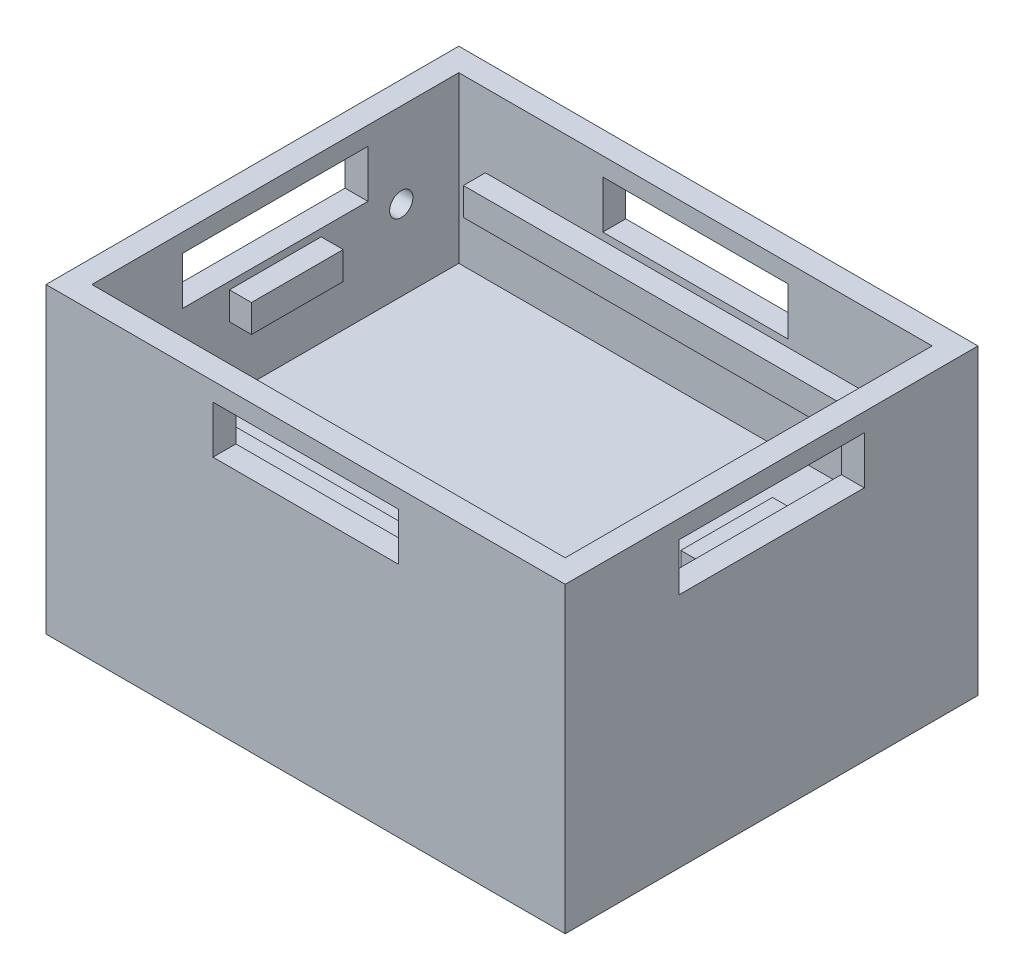
SolidWorks part; units mm, degrees
ref_plane "Front Plane" through (0, 0, 0) normal (0, 0, 1) x (1, 0, 0)
ref_plane "Top Plane" through (0, 0, 0) normal (0, 1, 0) x (1, 0, 0)
ref_plane "Right Plane" through (0, 0, 0) normal (1, 0, 0) x (0, 0, -1)
sketch "Sketch1" plane through (0, 0, 0) normal (0, 1, 0) x (1, 0, 0)
  line L0 (-2.5, 2.5) -> (-2.5, 202.5)
  line L5 (-15, -10) -> (268, -10)
  line L6 (-15, -10) -> (-15, 215)
  line L7 (-15, 215) -> (268, 215)
  line L8 (268, -10) -> (268, 215)
  line L9 (-2.5, 202.5) -> (255.5, 202.5)
  line L10 (255.5, 2.5) -> (255.5, 202.5)
  line L11 (-2.5, 2.5) -> (255.5, 2.5)
  dimension "D1" = 283
  dimension "D2" = 225
  dimension "D3" = 12.5
extrude "Walls" add sketch "Sketch1" along normal blind 90
sketch "Sketch3" plane through (0, 0, 0) normal (0, -1, 0) x (1, 0, 0)
  line L0 (268, -215) -> (-15, -215) construction
  line L1 (268, 10) -> (268, -215) construction
  line L2 (-15, 10) -> (268, 10) construction
  line L3 (-15, -215) -> (-15, 10) construction
  line L4 (268, -215) -> (-15, -215)
  line L5 (268, 10) -> (268, -215)
  line L6 (-15, 10) -> (268, 10)
  line L7 (-15, -215) -> (-15, 10)
extrude "Base" add sketch "Sketch3" along normal blind 12.5
ref_plane "Long_Support_Midplane" through (126.5, 0, 0) normal (1, 0, 0) x (0, 0, -1)
sketch "Sketch4" plane through (126.5, 0, 0) normal (1, 0, 0) x (0, 0, -1)
  line L0 (2.5, 0) -> (2.5, 90)
  line L1 (2.5, 50) -> (14.5, 50)
  line L2 (2.5, 50) -> (2.5, 34.9)
  line L3 (2.5, 34.9) -> (14.5, 34.9)
  line L4 (14.5, 50) -> (14.5, 34.9)
  line L5 (2.5, 0) -> (2.5, 90) construction
  line L6 (202.5, 50) -> (190.5, 50)
  line L7 (202.5, 50) -> (202.5, 34.9)
  line L8 (202.5, 34.9) -> (190.5, 34.9)
  line L9 (190.5, 50) -> (190.5, 34.9)
  line L14 (2.5, 0) -> (202.5, 0)
  line L15 (202.5, 0) -> (202.5, 90)
  line L16 (202.5, 90) -> (2.5, 90)
  line L17 (2.5, 90) -> (2.5, 0)
  line L18 (2.5, 0) -> (202.5, 0) construction
  line L19 (202.5, 0) -> (202.5, 90) construction
  line L20 (202.5, 90) -> (2.5, 90) construction
  line L21 (2.5, 90) -> (2.5, 0) construction
  dimension "D1" = 15.1
  dimension "D2" = 12
  dimension "D4" = 50
extrude "Long_Support" add sketch "Sketch4" along normal mid plane 229
ref_plane "Short_Support_Midplane" through (0, 0, -102.5) normal (0, 0, -1) x (-1, 0, 0)
sketch "Sketch5" plane through (0, 0, -102.5) normal (0, 0, -1) x (-1, 0, 0)
  line L1 (-255.5, 50) -> (-243.5, 50)
  line L2 (-255.5, 50) -> (-255.5, 34.9)
  line L3 (-255.5, 34.9) -> (-243.5, 34.9)
  line L4 (-243.5, 50) -> (-243.5, 34.9)
  line L5 (2.5, 50) -> (-9.5, 50)
  line L6 (2.5, 50) -> (2.5, 34.9)
  line L7 (2.5, 34.9) -> (-9.5, 34.9)
  line L8 (-9.5, 50) -> (-9.5, 34.9)
  line L12 (-255.5, 0) -> (2.5, 0)
  line L13 (2.5, 0) -> (2.5, 90)
  line L14 (2.5, 90) -> (-255.5, 90)
  line L15 (2.5, 0) -> (2.5, 90) construction
  line L16 (-255.5, 0) -> (2.5, 0) construction
  line L20 (-255.5, 90) -> (-255.5, 0)
  line L21 (-255.5, 90) -> (-255.5, 0) construction
  line L22 (2.5, 90) -> (-255.5, 90) construction
  dimension "D4" = 50
  dimension "D2" = 15.1
extrude "Short_Support" add sketch "Sketch5" along normal mid plane 50
sketch "Sketch6" plane through (-2.5, 0, 0) normal (1, 0, 0) x (0, 0, -1)
  line L4 (2.5, 0) -> (202.5, 0)
  line L5 (202.5, 0) -> (202.5, 90)
  line L6 (202.5, 90) -> (2.5, 90)
  line L7 (2.5, 90) -> (2.5, 0)
  line L8 (2.5, 0) -> (202.5, 0) construction
  line L9 (202.5, 0) -> (202.5, 90) construction
  line L10 (202.5, 90) -> (2.5, 90) construction
  line L11 (2.5, 90) -> (2.5, 0) construction
  circle A0 centre (171.15, 43.65) radius 6.35
  dimension "D2" = 12.7
  dimension "D3" = 31.35
  dimension "D4" = 43.65
extrude "Reservoir_Outflow_Tube_Hole" cut sketch "Sketch6" against normal up to next
sketch "Sketch7" plane through (-2.5, 0, 0) normal (1, 0, 0) x (0, 0, -1)
  line L0 (127.5, 50) -> (77.5, 50) construction
  line L1 (52, 54) -> (153, 54)
  line L2 (52, 54) -> (52, 80)
  line L3 (52, 80) -> (153, 80)
  line L4 (153, 54) -> (153, 80)
  line L5 (202.5, 90) -> (2.5, 90) construction
  line L7 (102.5, 80) -> (102.5, 54) construction
  line L8 (102.5, -27.5) -> (102.5, 27.5) construction
  dimension "D1" = 4
  dimension "D2" = 10
  dimension "D3" = 26
  dimension "D4" = 101
extrude "Connector_Port_ShortSide" cut sketch "Sketch7" against normal up to surface (12.5 mm away) up to face at (-15, 43.65, -177.5)
pattern_linear "LPattern1" count 2 spacing 270.5 along (1, 0, 0) of "Connector_Port_ShortSide"
sketch "Sketch8" plane through (0, 0, -2.5) normal (0, 0, 1) x (1, 0, 0)
  line L1 (76, 54) -> (177, 54)
  line L2 (76, 54) -> (76, 80)
  line L3 (76, 80) -> (177, 80)
  line L4 (177, 54) -> (177, 80)
  line L6 (241, 50) -> (12, 50) construction
  line L7 (126.5, 80) -> (126.5, 54) construction
  line L9 (-2.5, 90) -> (255.5, 90) construction
  line L10 (126.5, -28.05) -> (126.5, 28.05) construction
  dimension "D3" = 26
  dimension "D4" = 101
  dimension "D1" = 4
  dimension "D2" = 10
extrude "Connector_Port_LongSide" cut sketch "Sketch8" along normal up to surface (12.5 mm away) contours L4 L3 L2 L1 up to face at (126.5, 38.75, 10)
pattern_linear "LPattern2" count 2 spacing 212.5 along (0, 0, -1) of "Connector_Port_LongSide"
sketch "Sketch9" plane through (0, -12.5, 0) normal (0, -1, 0) x (1, 0, 0)
  line L10 (268, -215) -> (268, 10) construction
  line L11 (-15, -215) -> (268, -215) construction
  line L12 (268, 10) -> (-15, 10) construction
  line L13 (-15, 10) -> (-15, -215) construction
  line L14 (-2.5, -202.5) -> (255.5, -202.5)
  line L15 (255.5, -202.5) -> (255.5, -2.5)
  line L16 (255.5, -2.5) -> (-2.5, -2.5)
  line L17 (-2.5, -2.5) -> (-2.5, -202.5)
  line L18 (-2.5, -202.5) -> (255.5, -202.5)
  line L19 (255.5, -202.5) -> (255.5, -2.5)
  line L20 (255.5, -2.5) -> (-2.5, -2.5)
  line L21 (-2.5, -2.5) -> (-2.5, -202.5)
  line L22 (268, -215) -> (268, 10)
  line L23 (-15, -215) -> (268, -215)
  line L24 (268, 10) -> (-15, 10)
  line L25 (-15, 10) -> (-15, -215)
  dimension "D1" = 12.5
extrude "Lower_Water_Jacket_Walls" add sketch "Sketch9" along normal blind 50
sketch "Sketch11" plane through (0, -62.5, 0) normal (0, -1, 0) x (1, 0, 0)
  line L0 (-15, -215) -> (268, -215) construction
  line L1 (268, -215) -> (268, 10) construction
  line L2 (268, 10) -> (-15, 10) construction
  line L3 (-15, 10) -> (-15, -215) construction
  line L4 (-15, -215) -> (268, -215)
  line L5 (268, -215) -> (268, 10)
  line L6 (268, 10) -> (-15, 10)
  line L7 (-15, 10) -> (-15, -215)
extrude "Lower_Water_Jacket_Bottom" add sketch "Sketch11" along normal blind 12.5
ref_plane "ReservoirTop" through (0, 90, 0) normal (0, 1, 0) x (1, 0, 0)
ref_plane "MidLong" through (126.5, 0, 0) normal (1, 0, 0) x (0, 0, -1)
ref_plane "MidShort" through (0, 0, -102.5) normal (0, 0, 1) x (1, 0, 0)
equation "\"Length\"= 283mm"
equation "\"Width\"= 225mm"
equation "\"WallThickness\"= 12.5mm"
equation "\"UpperWaterJacketThickness\"= 28mm"
equation "\"SpacerHeight\"= 80.2mm"
equation "\"PlateLength\"= 252mm"
equation "\"PlateWidth\"= 190mm"
equation "\"PlateHoleDiameter\"= 5.9mm"
equation "\"PlateHoleBottom\"= 2mm"
equation "\"PlateHoleSide\"= 1.55mm"
equation "\"PlateHoleSpacing\"= 3.1mm"
equation "\"PlateThickness\"= 1.55mm"
equation "\"D1@Sketch1\"=\"Length\""
equation "\"D2@Sketch1\"=\"Width\""
equation "\"D3@Sketch1\"=\"WallThickness\""
equation "\"ReservoirBottom\"= 12.5mm"
equation "\"D1@Base\"=\"ReservoirBottom\""
equation "\"ReservoirSupportWidth\"= 12mm"
equation "\"D2@Sketch4\"=\"ReservoirSupportWidth\""
equation "\"ReservoirSupportHeight\"= 15.1mm"
equation "\"D1@Sketch4\"=\"ReservoirSupportHeight\""
equation "\"D1@Sketch5\"=\"ReservoirSupportWidth\""
equation "\"D2@Sketch5\"=\"ReservoirSupportHeight\""
equation "\"ReservoirSupportPlacementHeight\"= 50mm"
equation "\"D4@Sketch5\"=\"ReservoirSupportPlacementHeight\""
equation "\"D4@Sketch4\"=\"ReservoirSupportPlacementHeight\""
equation "\"ReservoirHoleDiameter\"= 12.7mm"
equation "\"D2@Sketch6\"=\"ReservoirHoleDiameter\""
equation "\"ReservoirHoleRight\"= 25mm"
equation "\"D3@Sketch6\"=\"ReservoirHoleRight\"+\"ReservoirHoleDiameter\"/2"
equation "\"ReservoirHoleTop\"= \"ReservoirSupportPlacementHeight\""
equation "\"D4@Sketch6\"=\"ReservoirHoleTop\"-\"ReservoirHoleDiameter\"/2"
equation "\"ReservoirHeight\"= 90mm"
equation "\"D1@Walls\"=\"ReservoirHeight\""
equation "\"ReservoirPortBottom\"= 4mm"
equation "\"D1@Sketch7\"=\"ReservoirPortBottom\""
equation "\"ReservoirPortTop\"= 10mm"
equation "\"D2@Sketch7\"=\"ReservoirPortTop\""
equation "\"ReservoirPortWidth\"= 101mm"
equation "\"D4@Sketch7\"=\"ReservoirPortWidth\""
equation "\"D4@Sketch8\"=\"ReservoirPortWidth\""
equation "\"D1@Sketch8\"=\"ReservoirPortBottom\""
equation "\"D2@Sketch8\"=\"ReservoirPortTop\""
equation "\"D1@Sketch9\"=\"WallThickness\""
equation "\"LowerWaterJacketHeight\"= 50"
equation "\"D1@Lower_Water_Jacket_Walls\" = \"LowerWaterJacketHeight\""
equation "\"LowerWaterJacketBottomThickness\"= \"WallThickness\""
equation "\"D1@Lower_Water_Jacket_Bottom\" = \"LowerWaterJacketBottomThickness\""
